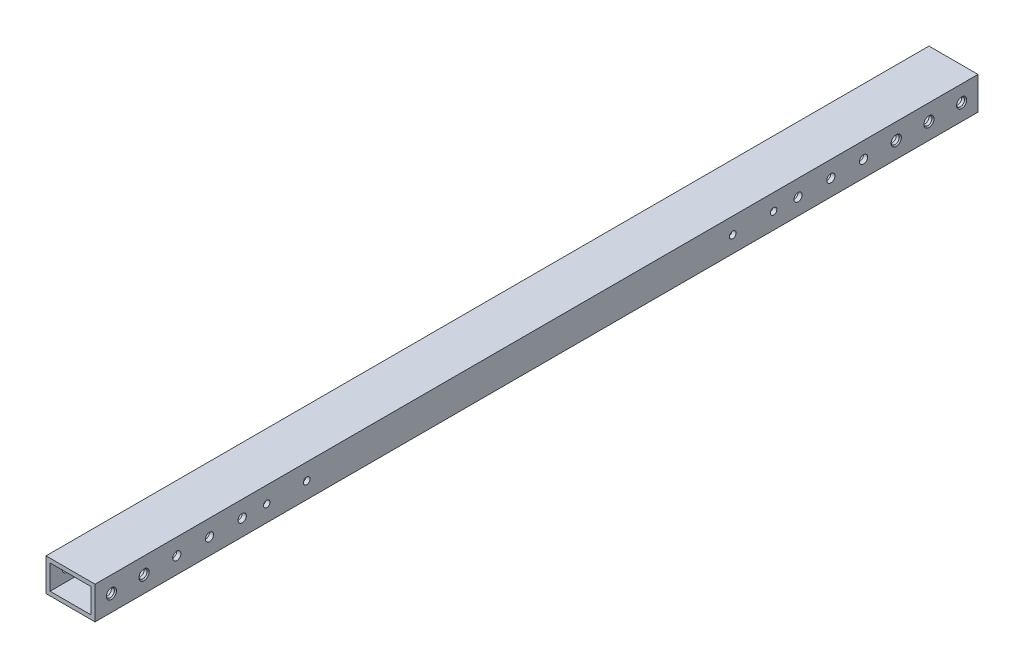
SolidWorks part; units mm, degrees
ref_plane "Front Plane" through (0, 0, 0) normal (0, 0, 1) x (1, 0, 0)
ref_plane "Top Plane" through (0, 0, 0) normal (0, 1, 0) x (1, 0, 0)
ref_plane "Right Plane" through (0, 0, 0) normal (1, 0, 0) x (0, 0, -1)
sketch "Sketch1" plane through (0, 0, 0) normal (0, 0, 1) x (1, 0, 0)
  line L0 (-15.875, 9.525) -> (15.875, 9.525)
  line L2 (-19.05, 12.7) -> (19.05, 12.7)
  line L3 (-19.05, 12.7) -> (-19.05, -12.7)
  line L4 (-19.05, -12.7) -> (19.05, -12.7)
  line L5 (19.05, 12.7) -> (19.05, -12.7)
  line L10 (15.875, 9.525) -> (15.875, -9.525)
  line L11 (-15.875, -9.525) -> (15.875, -9.525)
  line L12 (-15.875, 9.525) -> (-15.875, -9.525)
  point P12 (0, 12.7)
  point P14 (19.05, 0)
  dimension "Wall Thickness" = 3.175
  dimension "Outside Width" = 38.1
  dimension "Outside Height" = 25.4
  dimension "Inside Height" = 19.05
  dimension "Inside Width" = 31.75
sketch "Sketch2" plane through (0, 0, 0) normal (1, 0, 0) x (0, 0, -1)
  line L0 (342.9, 0) -> (-342.9, 0)
  point P4 (0, 0)
  point P7 (-342.9, 0)
  point P10 (342.9, 0)
  dimension "Length" = 685.8
sketch "Sketch3" plane through (0, 0, 0) normal (0, 0, 1) x (1, 0, 0)
  line L21 (19.05, 12.7) -> (-19.05, 12.7)
  line L22 (19.05, -12.7) -> (19.05, 12.7)
  line L23 (-19.05, -12.7) -> (19.05, -12.7)
  line L24 (-19.05, 12.7) -> (-19.05, -12.7)
  line L25 (19.05, 12.7) -> (-19.05, 12.7)
  line L26 (19.05, -12.7) -> (19.05, 12.7)
  line L27 (-19.05, -12.7) -> (19.05, -12.7)
  line L28 (-19.05, 12.7) -> (-19.05, -12.7)
  line L29 (15.875, 9.525) -> (-15.875, 9.525)
  line L30 (15.875, -9.525) -> (15.875, 9.525)
  line L31 (-15.875, -9.525) -> (15.875, -9.525)
  line L32 (-15.875, 9.525) -> (-15.875, -9.525)
  line L33 (15.875, 9.525) -> (-15.875, 9.525)
  line L34 (15.875, -9.525) -> (15.875, 9.525)
  line L35 (-15.875, -9.525) -> (15.875, -9.525)
  line L36 (-15.875, 9.525) -> (-15.875, -9.525)
  dimension "D1" = 0
  dimension "D2" = 0
extrude "Boss-Extrude1" add sketch "Sketch3" along normal up to vertex (342.9 mm away) and the other way up to vertex (342.9 mm away) up to point (0, 0, 342.9) other way up to point (0, 0, -342.9)
sketch "Drawing Reference" plane through (0, 0, 0) normal (1, 0, 0) x (0, 0, -1)
  line L0 (-342.9, 0) -> (342.9, 0) construction
  line L1 (0, -12.7) -> (0, 12.7) construction
  line L2 (-342.9, -12.7) -> (342.9, -12.7) construction
  line L5 (-342.9, 12.7) -> (342.9, 12.7) construction
  point P7 (-315.468, 0)
  point P8 (315.468, 0)
  dimension "D1" = 27.432
sketch "Sketch4" plane through (-19.05, 0, 0) normal (-1, 0, 0) x (0, 0, 1)
  line L0 (-342.9, 0) -> (-330.2, 0)
  line L1 (-342.9, 12.7) -> (-342.9, -12.7) construction
  line L2 (-330.2, 0) -> (-304.8, 0)
  line L3 (-304.8, 0) -> (-279.4, 0)
  line L4 (-279.4, 0) -> (-254, 0)
  line L5 (-254, 0) -> (-228.6, 0)
  line L6 (-228.6, 0) -> (-203.2, 0)
  line L7 (342.9, 0) -> (330.2, 0)
  line L8 (342.9, 12.7) -> (342.9, -12.7) construction
  line L9 (330.2, 0) -> (304.8, 0)
  line L10 (304.8, 0) -> (279.4, 0)
  line L11 (279.4, 0) -> (254, 0)
  line L12 (254, 0) -> (228.6, 0)
  line L13 (-203.2, 0) -> (-184.15, 0)
  line L14 (-203.2, 0) -> (-152.4, 0) construction
  line L15 (228.6, 0) -> (209.55, 0)
  line L16 (228.6, 0) -> (178.5118, 0) construction
hole_wizard "1/4 (0.25) Diameter Hole2" positions "Sketch7" profile "Sketch8" hole size "1/4" standard "ANSI Inch" end condition through all
sketch "Sketch7" plane through (-19.05, 0, 0) normal (-1, 0, 0) x (0, 0, 1)
  point P0 (-330.2, 0)
  point P3 (-304.8, 0)
  point P7 (330.2, 0)
  point P11 (-279.4, 0)
  point P14 (304.8, 0)
sketch "Sketch8" plane through (-19.05, 0, -330.2) normal (0, 1, 0) x (0, 0, 1)
  line L0 (0, 0) -> (0, 38.1)
  line L1 (0, 38.1) -> (3.9624, 38.1)
  line L2 (3.175, 37.1942) -> (3.175, 0)
  line L5 (3.175, 0) -> (0, 0)
  line L7 (3.9624, 38.1) -> (3.175, 37.1942)
  line L8 (-3.9624, 38.1) -> (-3.175, 37.1942) construction
  line L11 (0, -6.35) -> (0, 107.95) construction
  dimension "Thru Hole Dia." = 6.35
  dimension "Thru Hole Depth" = 38.1
  dimension "Far C'Sink Dia." = 7.9248
  dimension "Far C'Sink Angle" = 82
hole_wizard "1/4 (0.25) Diameter Hole3" positions "Sketch9" profile "Sketch10" hole size "1/4" standard "ANSI Inch" end condition through all
sketch "Sketch9" plane through (19.05, 0, 0) normal (1, 0, 0) x (0, 0, -1)
  point P0 (-279.4, 0)
  point P3 (-254, 0)
  point P6 (-228.6, 0)
  point P9 (254, 0)
  point P12 (228.6, 0)
  point P15 (203.2, 0)
sketch "Sketch10" plane through (19.05, 0, 279.4) normal (0, 1, 0) x (0, 0, -1)
  line L0 (0, 0) -> (0, 38.1)
  line L1 (0, 38.1) -> (3.175, 38.1)
  line L2 (3.175, 38.1) -> (3.175, 0)
  line L5 (3.175, 0) -> (0, 0)
  line L11 (0, -6.35) -> (0, 107.95) construction
  dimension "Thru Hole Dia." = 6.35
  dimension "Thru Hole Depth" = 38.1
hole_wizard "13/64 (0.20313) Diameter Hole1" positions "Sketch11" profile "Sketch12" hole size "13/64" standard "ANSI Inch" end condition through all
sketch "Sketch11" plane through (19.05, 0, 0) normal (1, 0, 0) x (0, 0, -1)
  point P0 (152.4, 0)
  point P3 (-178.5118, 0)
sketch "Sketch12" plane through (19.05, 0, -152.4) normal (0, 1, 0) x (0, 0, -1)
  line L0 (0, 0) -> (0, 38.1)
  line L1 (0, 38.1) -> (2.5798, 38.1)
  line L2 (2.5798, 38.1) -> (2.5798, 0)
  line L5 (2.5798, 0) -> (0, 0)
  line L11 (0, -6.35) -> (0, 107.95) construction
  dimension "Thru Hole Dia." = 5.1595
  dimension "Thru Hole Depth" = 38.1
hole_wizard "#10 Clearance Hole1" positions "Sketch13" profile "Sketch14" hole size "#10" standard "ANSI Inch" end condition through all
sketch "Sketch13" plane through (-19.05, 0, 0) normal (-1, 0, 0) x (0, 0, 1)
  point P0 (-184.15, 0)
  point P3 (209.55, 0)
sketch "Sketch14" plane through (-19.05, 0, -184.15) normal (0, 1, 0) x (0, 0, 1)
  line L0 (0, 0) -> (0, 38.1)
  line L1 (0, 38.1) -> (2.4892, 38.1)
  line L2 (2.4892, 38.1) -> (2.4892, 0)
  line L5 (2.4892, 0) -> (0, 0)
  line L11 (0, -6.35) -> (0, 107.95) construction
  dimension "Thru Hole Dia." = 4.9784
  dimension "Thru Hole Depth" = 38.1
equation "\"D1@Drawing Reference\"=\"Outside Width@Sketch1\" * 0.72"
